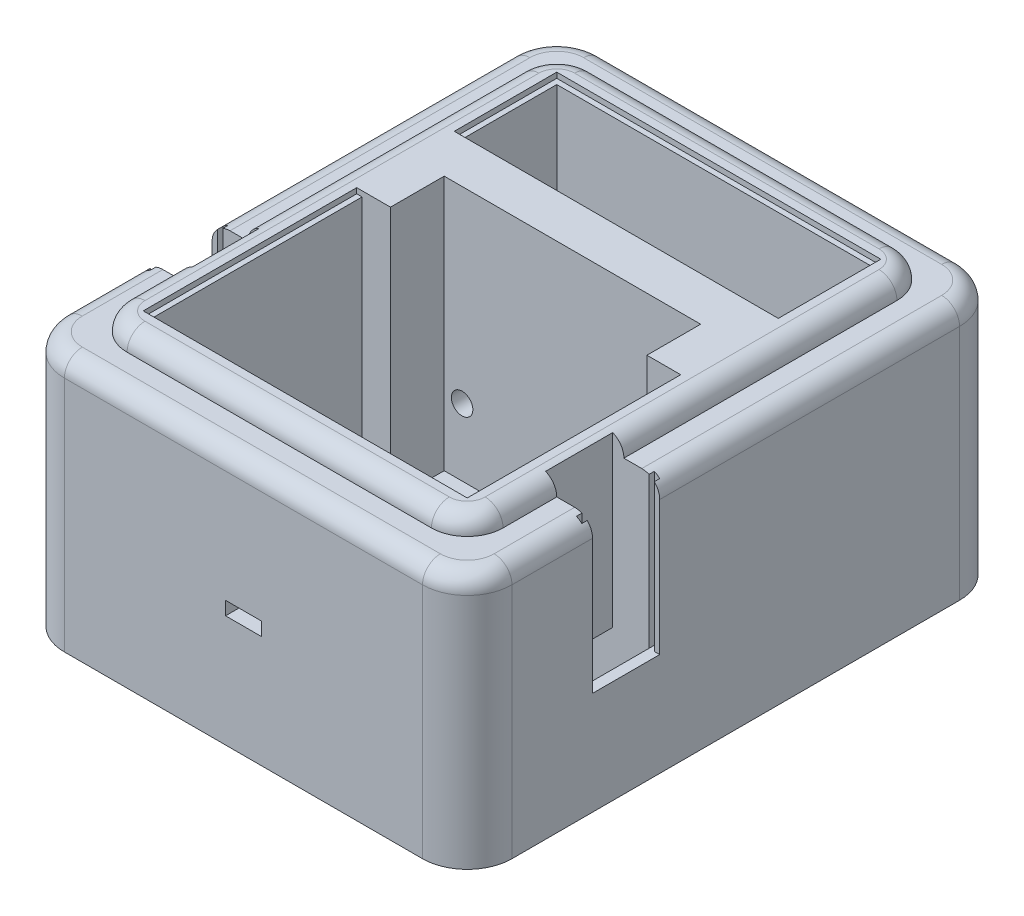
SolidWorks part; units mm, degrees
ref_plane "Přední rovina" through (0, 0, 0) normal (0, 0, 1) x (1, 0, 0)
ref_plane "Horní rovina" through (0, 0, 0) normal (0, 1, 0) x (1, 0, 0)
ref_plane "Pravá rovina" through (0, 0, 0) normal (1, 0, 0) x (0, 0, -1)
sketch "Skica2" plane through (0, 0, 0) normal (0, 1, 0) x (1, 0, 0)
  line L1 (0, 0) -> (100, 0)
  line L2 (0, 0) -> (0, 120)
  line L3 (0, 120) -> (100, 120)
  line L4 (100, 0) -> (100, 120)
  dimension "D1" = 120
  dimension "D2" = 100
extrude "Přidat vysunutím1" add sketch "Skica2" along normal blind 4
sketch "Skica3" plane through (0, 4, 0) normal (0, 1, 0) x (1, 0, 0)
  line L0 (0, 0) -> (100, 0) construction
  line L1 (0, 120) -> (15, 120)
  line L2 (0, 120) -> (0, 0)
  line L3 (0, 0) -> (15, 0)
  line L4 (15, 120) -> (15, 0)
  line L5 (100, 0) -> (100, 120) construction
  line L6 (0, 120) -> (100, 120)
  line L7 (0, 120) -> (0, 105)
  line L8 (0, 105) -> (100, 105)
  line L9 (100, 120) -> (100, 105)
  line L11 (100, 120) -> (85, 120)
  line L12 (100, 120) -> (100, 0)
  line L13 (100, 0) -> (85, 0)
  line L14 (85, 120) -> (85, 0)
  line L15 (100, 0) -> (0, 0)
  line L16 (100, 0) -> (100, 15)
  line L17 (100, 15) -> (0, 15)
  line L18 (0, 0) -> (0, 15)
  line L19 (15, 76.5) -> (85, 76.5)
  line L20 (15, 76.5) -> (15, 61.5)
  line L21 (15, 61.5) -> (85, 61.5)
  line L22 (85, 76.5) -> (85, 61.5)
  line L23 (21.35, 61.5) -> (78.65, 61.5)
  line L24 (21.35, 61.5) -> (21.35, 73.5)
  line L25 (21.35, 73.5) -> (78.65, 73.5)
  line L26 (78.65, 61.5) -> (78.65, 73.5)
  line L27 (15, 76.5) -> (85, 76.5)
  line L28 (15, 76.5) -> (15, 84.5)
  line L29 (15, 84.5) -> (85, 84.5)
  line L30 (85, 76.5) -> (85, 84.5)
  line L31 (21.35, 61.5) -> (15, 61.5)
  line L32 (21.35, 61.5) -> (21.35, 76.5)
  line L33 (21.35, 76.5) -> (15, 76.5)
  line L34 (15, 61.5) -> (15, 76.5)
  line L35 (78.65, 61.5) -> (85, 61.5)
  line L36 (78.65, 61.5) -> (78.65, 76.5)
  line L37 (78.65, 76.5) -> (85, 76.5)
  line L38 (85, 61.5) -> (85, 76.5)
  line L39 (78.65, 73.5) -> (21.35, 73.5)
  line L40 (78.65, 73.5) -> (78.65, 76.5)
  line L41 (78.65, 76.5) -> (21.35, 76.5)
  line L42 (21.35, 73.5) -> (21.35, 76.5)
  line M25 (0, 120) -> (0, 0)
  line M26 (0, 0) -> (100, 0)
  line M27 (100, 0) -> (100, 120)
  line M28 (100, 120) -> (0, 120)
  dimension "D1" = 15
  dimension "D2" = 15
  dimension "D3" = 15
  dimension "D4" = 15
  dimension "D5" = 15
  dimension "D6" = 70
  dimension "D7" = 12
  dimension "D8" = 57.3
  dimension "D9" = 6.35
  dimension "D10" = 28.5
  dimension "D11" = 8
  dimension "D12" = 70
extrude "Přidat vysunutím2" add sketch "Skica3" along normal blind 50 contours L8 L4 M25 M28 | L14 L6 L4 L8 | L17 L4 L8 L2 | L14 L8 M28 M27 | L17 L12 L8 L14 | L29 L4 L19 L27 L14 | L4 L17 M25 M26 | L14 L17 L4 M26 | L17 L14 M27 M26 | L24 L32 L19 L4 L21 | L25 L36 L27 L32 | L36 L26 L21 L14 L19
sketch "Skica4" plane through (0, 4, 0) normal (0, 1, 0) x (1, 0, 0)
  line L1 (15, 105) -> (85, 105)
  line L2 (15, 105) -> (15, 84.5)
  line L3 (15, 84.5) -> (85, 84.5)
  line L4 (85, 105) -> (85, 84.5)
extrude "Přidat vysunutím3" add sketch "Skica4" along normal blind 23
sketch "Skica8" plane through (0, 0, -61.5) normal (0, 0, 1) x (1, 0, 0)
  line L0 (78.65, 54) -> (78.65, 4) construction
  line L1 (78.65, 33) -> (85, 33)
  line L2 (78.65, 33) -> (78.65, 27)
  line L3 (78.65, 27) -> (85, 27)
  line L4 (85, 33) -> (85, 27)
  line L5 (85, 54) -> (85, 4) construction
  line L6 (78.65, 54) -> (85, 54) construction
  dimension "D1" = 6
  dimension "D2" = 21
extrude "Odebrat vysunutím1" cut sketch "Skica8" against normal blind 23
sketch "Skica9" plane through (0, 27, 0) normal (0, 1, 0) x (1, 0, 0)
  line L1 (78.65, 61.5) -> (85, 61.5)
  line L2 (78.65, 61.5) -> (78.65, 63.5)
  line L3 (78.65, 63.5) -> (85, 63.5)
  line L4 (85, 61.5) -> (85, 63.5)
  line L5 (85, 61.5) -> (85, 105) construction
  dimension "D1" = 2
  dimension "D2" = 6.35
extrude "Přidat vysunutím5" add sketch "Skica9" along normal blind 6
sketch "Skica10" plane through (0, 0, -73.5) normal (0, 0, 1) x (1, 0, 0)
  line L0 (21.35, 54) -> (78.65, 54) construction
  line L1 (78.65, 27) -> (78.65, 4) construction
  line L2 (21.35, 54) -> (21.35, 4) construction
  circle A0 centre (25.35, 19) radius 2.4
  circle A1 centre (74.65, 19) radius 2.4
  dimension "D1" = 4.8
  dimension "D2" = 4.8
  dimension "D5" = 4
  dimension "D6" = 4
  dimension "D3" = 35
  dimension "D4" = 35
extrude "Odebrat vysunutím2" cut sketch "Skica10" against normal blind 8
sketch "Skica11" plane through (0, 0, -15) normal (0, 0, -1) x (-1, 0, 0)
  line L0 (-85, 4) -> (-15, 4) construction
  line L1 (-58.3, 30.8) -> (-41.7, 30.8)
  line L2 (-58.3, 30.8) -> (-58.3, 19)
  line L3 (-58.3, 19) -> (-41.7, 19)
  line L4 (-41.7, 30.8) -> (-41.7, 19)
  line L5 (-15, 54) -> (-15, 4) construction
  dimension "D1" = 11.8
  dimension "D2" = 16.6
  dimension "D3" = 15
  dimension "26.7" = 26.7
extrude "Odebrat vysunutím5" cut sketch "Skica11" against normal blind 10
sketch "Skica14" plane through (0, 0, 0) normal (0, 0, 1) x (1, 0, 0)
  line L0 (0, 0) -> (100, 0) construction
  line L1 (46, 28) -> (54, 28)
  line L2 (46, 28) -> (46, 25)
  line L3 (46, 25) -> (54, 25)
  line L4 (54, 28) -> (54, 25)
  line L5 (0, 54) -> (0, 0) construction
  dimension "D1" = 3
  dimension "D2" = 8
  dimension "D3" = 25
  dimension "D4" = 46
extrude "Odebrat vysunutím6" cut sketch "Skica14" against normal blind 5
sketch "Skica15" plane through (0, 54, 0) normal (0, 1, 0) x (1, 0, 0)
  line L0 (0, 0) -> (100, 0) construction
  line L1 (0, 120) -> (8, 120)
  line L2 (0, 120) -> (0, 0)
  line L3 (0, 0) -> (8, 0)
  line L4 (8, 120) -> (8, 0)
  line L5 (100, 120) -> (0, 120) construction
  line L6 (100, 0) -> (0, 0)
  line L7 (100, 0) -> (100, 8)
  line L8 (100, 8) -> (0, 8)
  line L9 (0, 0) -> (0, 8)
  line L10 (100, 0) -> (92, 0)
  line L11 (100, 0) -> (100, 120)
  line L12 (100, 120) -> (92, 120)
  line L13 (92, 0) -> (92, 120)
  line L15 (0, 120) -> (100, 120)
  line L16 (0, 120) -> (0, 112)
  line L17 (0, 112) -> (100, 112)
  line L18 (100, 120) -> (100, 112)
  dimension "D1" = 8
  dimension "D2" = 8
  dimension "D3" = 8
  dimension "D4" = 8
extrude "Odebrat vysunutím7" cut sketch "Skica15" against normal blind 4
sketch "Skica20" plane through (0, 0, 0) normal (-1, 0, 0) x (0, 0, 1)
  line L0 (-112, 54) -> (-8, 54) construction
  line L1 (-43, 54) -> (-28, 54)
  line L2 (-43, 54) -> (-43, 23)
  line L3 (-43, 23) -> (-28, 23)
  line L4 (-28, 54) -> (-28, 23)
  line L6 (-8, 50) -> (-8, 54) construction
  dimension "D1" = 31
  dimension "D2" = 15
  dimension "D3" = 20
extrude "Odebrat vysunutím8" cut sketch "Skica20" against normal blind 10
sketch "Skica21" plane through (100, 0, 0) normal (1, 0, 0) x (0, 0, -1)
  line L0 (8, 54) -> (112, 54) construction
  line L1 (28, 54) -> (43, 54)
  line L2 (28, 54) -> (28, 23)
  line L3 (28, 23) -> (43, 23)
  line L4 (43, 54) -> (43, 23)
  line L5 (8, 50) -> (8, 54) construction
  dimension "D1" = 31
  dimension "D2" = 15
  dimension "D3" = 20
extrude "Odebrat vysunutím10" cut sketch "Skica21" against normal blind 10
sketch "Skica22" plane through (10, 0, 0) normal (-1, 0, 0) x (0, 0, 1)
  line L0 (-43, 54) -> (-43, 23) construction
  line L1 (-43, 23) -> (-28, 23) construction
  circle A0 centre (-35.5, 31.3) radius 2.2
  dimension "D1" = 4.4
  dimension "D2" = 7.5
  dimension "D3" = 8.3
extrude "Odebrat vysunutím11" cut sketch "Skica22" against normal blind 3
sketch "Skica23" plane through (90, 0, 0) normal (1, 0, 0) x (0, 0, -1)
  line L0 (28, 50) -> (28, 23) construction
  line L1 (28, 23) -> (43, 23) construction
  circle A0 centre (35.5, 31.3) radius 2.2
  dimension "D1" = 4.4
  dimension "D2" = 7.5
  dimension "D3" = 8.3
extrude "Odebrat vysunutím12" cut sketch "Skica23" against normal blind 3
sketch "Skica24" plane through (0, 50, 0) normal (0, 1, 0) x (1, 0, 0)
  line L0 (10, 28) -> (0, 28) construction
  line L1 (1.2, 28) -> (2.4, 28)
  line L2 (1.2, 28) -> (1.2, 26.8)
  line L3 (1.2, 26.8) -> (2.4, 26.8)
  line L4 (2.4, 28) -> (2.4, 26.8)
  line L5 (0, 28) -> (0, 0) construction
  line L6 (10, 43) -> (0, 43) construction
  line L7 (1.2, 43) -> (2.4, 43)
  line L8 (1.2, 43) -> (1.2, 44.2)
  line L9 (1.2, 44.2) -> (2.4, 44.2)
  line L10 (2.4, 43) -> (2.4, 44.2)
  line L11 (0, 120) -> (0, 43) construction
  line L12 (92, 28) -> (100, 28) construction
  line L13 (97.6, 28) -> (98.8, 28)
  line L14 (97.6, 28) -> (97.6, 26.8)
  line L15 (97.6, 26.8) -> (98.8, 26.8)
  line L16 (98.8, 28) -> (98.8, 26.8)
  line L17 (100, 43) -> (92, 43) construction
  line L18 (97.6, 43) -> (98.8, 43)
  line L19 (97.6, 43) -> (97.6, 44.2)
  line L20 (97.6, 44.2) -> (98.8, 44.2)
  line L21 (98.8, 43) -> (98.8, 44.2)
  line L22 (100, 0) -> (100, 28) construction
  line L23 (100, 43) -> (100, 120) construction
  dimension "D1" = 1.2
  dimension "D2" = 1.2
  dimension "D3" = 1.2
  dimension "D4" = 1.2
  dimension "D5" = 1.2
  dimension "D6" = 1.2
  dimension "D7" = 1.2
  dimension "D8" = 1.2
  dimension "D9" = 1.2
extrude "Odebrat vysunutím14" cut sketch "Skica24" against normal blind 27
sketch "Skica26" plane through (0, 23, 0) normal (0, 1, 0) x (1, 0, 0)
  line L0 (15, 61.5) -> (15, 15) construction
  line L1 (2.4, 43) -> (15, 43)
  line L2 (2.4, 43) -> (2.4, 28)
  line L3 (2.4, 28) -> (15, 28)
  line L4 (15, 43) -> (15, 28)
  line L5 (85, 61.5) -> (85, 15) construction
  line L6 (97.6, 43) -> (85, 43)
  line L7 (97.6, 43) -> (97.6, 28)
  line L8 (97.6, 28) -> (85, 28)
  line L9 (85, 43) -> (85, 28)
  line L10 (85, 15) -> (15, 15) construction
  line L12 (85, 15) -> (15, 15) construction
  dimension "D1" = 13
  dimension "D2" = 13
extrude "Odebrat vysunutím16" cut sketch "Skica26" against normal blind 19
sketch "Skica32" plane through (13, 0, 0) normal (-1, 0, 0) x (0, 0, 1)
  circle A0 centre (-35.5, 31.3) radius 2.2
extrude "Odebrat vysunutím19" cut sketch "Skica32" against normal through all
sketch "Skica33" plane through (78.65, 0, 0) normal (-1, 0, 0) x (0, 0, 1)
  line L0 (-61.5, 54) -> (-61.5, 4) construction
  line L1 (-63.5, 33) -> (-61.5, 33)
  line L2 (-63.5, 33) -> (-63.5, 27)
  line L3 (-63.5, 27) -> (-61.5, 27)
  line L4 (-61.5, 33) -> (-61.5, 27)
extrude "Odebrat vysunutím20" cut sketch "Skica33" against normal up to surface (6.35 mm away) up to face at (85, 31.3, -37.7)
sketch "Skica35" plane through (0, 19, 0) normal (0, 1, 0) x (1, 0, 0)
  line L1 (41.7, 15) -> (58.3, 15)
  line L2 (41.7, 15) -> (41.7, 5)
  line L3 (41.7, 5) -> (58.3, 5)
  line L4 (58.3, 15) -> (58.3, 5)
extrude "Odebrat vysunutím21" cut sketch "Skica35" against normal blind 1.5
sketch "Skica38" plane through (0, 27, 0) normal (0, 1, 0) x (1, 0, 0)
  line L1 (78.65, 61.5) -> (79.65, 61.5)
  line L2 (78.65, 61.5) -> (78.65, 84.5)
  line L3 (78.65, 84.5) -> (79.65, 84.5)
  line L4 (79.65, 61.5) -> (79.65, 84.5)
  dimension "D1" = 1
extrude "Přidat vysunutím9" add sketch "Skica38" along normal blind 15
sketch "Skica39" plane through (0, 0, -61.5) normal (0, 0, 1) x (1, 0, 0)
  line L1 (79.65, 33) -> (85, 33)
  line L2 (79.65, 33) -> (79.65, 38)
  line L3 (79.65, 38) -> (85, 38)
  line L4 (85, 33) -> (85, 38)
  line L5 (85, 54) -> (85, 33) construction
  dimension "D1" = 5
  dimension "D2" = 5.35
extrude "Odebrat vysunutím23" cut sketch "Skica39" against normal up to surface (23 mm away) up to face at (59.8833, 38, -84.5)
sketch "Skica40" plane through (10, 0, 0) normal (-1, 0, 0) x (0, 0, 1)
  line L1 (-43, 54) -> (-28, 54)
  line L2 (-43, 54) -> (-43, 23)
  line L3 (-43, 23) -> (-28, 23)
  line L4 (-28, 54) -> (-28, 23)
extrude "Odebrat vysunutím24" cut sketch "Skica40" against normal blind 0.5
sketch "Skica41" plane through (90, 0, 0) normal (1, 0, 0) x (0, 0, -1)
  line L1 (28, 23) -> (43, 23)
  line L2 (28, 23) -> (28, 54)
  line L3 (28, 54) -> (43, 54)
  line L4 (43, 23) -> (43, 54)
extrude "Odebrat vysunutím25" cut sketch "Skica41" against normal blind 0.5
sketch "Skica43" plane through (0, 54, 0) normal (0, 1, 0) x (1, 0, 0)
  line L0 (92, 8) -> (8, 8) construction
  line L1 (8, 112) -> (85, 112)
  line L2 (8, 112) -> (8, 105)
  line L3 (8, 105) -> (85, 105)
  line L4 (85, 112) -> (85, 105)
  line L5 (85, 8) -> (92, 8)
  line L6 (85, 8) -> (85, 112)
  line L7 (85, 112) -> (92, 112)
  line L8 (92, 8) -> (92, 112)
  line L9 (15, 84.5) -> (85, 84.5) construction
  line L10 (8, 105) -> (15, 105)
  line L11 (8, 105) -> (8, 15)
  line L12 (8, 15) -> (15, 15)
  line L13 (15, 105) -> (15, 15)
  line L14 (8, 15) -> (85, 15)
  line L15 (8, 15) -> (8, 8)
  line L16 (8, 8) -> (85, 8)
  line L17 (85, 15) -> (85, 8)
  line L18 (78.65, 61.5) -> (85, 61.5)
  line L19 (78.65, 61.5) -> (78.65, 84.5)
  line L20 (78.65, 84.5) -> (85, 84.5)
  line L21 (85, 61.5) -> (85, 84.5)
  line L23 (15, 61.5) -> (21.35, 61.5)
  line L24 (15, 61.5) -> (15, 73.5)
  line L25 (15, 73.5) -> (21.35, 73.5)
  line L26 (21.35, 61.5) -> (21.35, 73.5)
  line L27 (78.65, 84.5) -> (15, 84.5)
  line L28 (78.65, 84.5) -> (78.65, 73.5)
  line L29 (78.65, 73.5) -> (15, 73.5)
  line L30 (15, 84.5) -> (15, 73.5)
extrude "Přidat vysunutím10" add sketch "Skica43" along normal blind 7 contours L4 L5 L3 L24 | L13 L23 L3 L5 L6 L7 L8 L9 L12 L15 | L19 L12 L6 L21 | L6 L10 L11 L0 L1 L2 L3 L4 L20 L13 | L13 L25 L18 L19 L21 | L25 L13 L16 L17 | L12 L9 L10 L6 L14
sketch "Skica44" plane through (0, 50, 0) normal (0, 1, 0) x (1, 0, 0)
  line L0 (8, 28) -> (8, 8) construction
  line L1 (0, 120) -> (2.4, 120)
  line L2 (0, 120) -> (0, 44.2)
  line L3 (0, 44.2) -> (2.4, 44.2)
  line L4 (2.4, 120) -> (2.4, 44.2)
  line L5 (0, 43) -> (1.2, 43)
  line L6 (0, 43) -> (0, 44.2)
  line L7 (0, 44.2) -> (1.2, 44.2)
  line L8 (1.2, 43) -> (1.2, 44.2)
  line L9 (0, 28) -> (1.2, 28)
  line L10 (0, 28) -> (0, 26.8)
  line L11 (0, 26.8) -> (1.2, 26.8)
  line L12 (1.2, 28) -> (1.2, 26.8)
  line L13 (2.4, 28) -> (8, 28)
  line L14 (2.4, 28) -> (2.4, 26.8)
  line L15 (2.4, 26.8) -> (8, 26.8)
  line L16 (8, 28) -> (8, 26.8)
  line L17 (92, 43) -> (92, 112) construction
  line L18 (8, 8) -> (0, 8)
  line L19 (8, 8) -> (8, 26.8)
  line L20 (8, 26.8) -> (0, 26.8)
  line L21 (0, 8) -> (0, 26.8)
  line L22 (0, 8) -> (100, 8)
  line L23 (0, 8) -> (0, 0)
  line L24 (0, 0) -> (100, 0)
  line L25 (100, 8) -> (100, 0)
  line L26 (92, 28) -> (97.6, 28)
  line L27 (92, 28) -> (92, 26.8)
  line L28 (92, 26.8) -> (97.6, 26.8)
  line L29 (97.6, 28) -> (97.6, 26.8)
  line L30 (100, 28) -> (98.8, 28)
  line L31 (100, 28) -> (100, 26.8)
  line L32 (100, 26.8) -> (98.8, 26.8)
  line L33 (98.8, 28) -> (98.8, 26.8)
  line L34 (92, 26.8) -> (100, 26.8)
  line L35 (92, 26.8) -> (92, 8)
  line L36 (92, 8) -> (100, 8)
  line L37 (100, 26.8) -> (100, 8)
  line L38 (100, 43) -> (98.8, 43)
  line L39 (100, 43) -> (100, 44.2)
  line L40 (100, 44.2) -> (98.8, 44.2)
  line L41 (98.8, 43) -> (98.8, 44.2)
  line L42 (97.6, 43) -> (92, 43)
  line L43 (97.6, 43) -> (97.6, 44.2)
  line L44 (97.6, 44.2) -> (92, 44.2)
  line L45 (92, 43) -> (92, 44.2)
  line L47 (92, 44.2) -> (100, 44.2)
  line L48 (92, 44.2) -> (92, 120)
  line L49 (92, 120) -> (100, 120)
  line L50 (100, 44.2) -> (100, 120)
  line L51 (2.4, 120) -> (92, 120)
  line L52 (2.4, 120) -> (2.4, 112)
  line L53 (2.4, 112) -> (92, 112)
  line L54 (92, 120) -> (92, 112)
  line L55 (8, 43) -> (2.4, 43)
  line L56 (8, 43) -> (8, 112)
  line L57 (8, 112) -> (2.4, 112)
  line L58 (2.4, 43) -> (2.4, 112)
  line M1 (1.2, 43) -> (1.2, 44.2)
  line M3 (2.4, 44.2) -> (2.4, 43)
  line M4 (2.4, 43) -> (8, 43)
  line M5 (8, 43) -> (8, 112)
  line M6 (8, 112) -> (92, 112)
  line M7 (92, 112) -> (92, 43)
  line M8 (92, 43) -> (97.6, 43)
  line M9 (97.6, 43) -> (97.6, 44.2)
  line M10 (97.6, 44.2) -> (98.8, 44.2)
  line M11 (98.8, 44.2) -> (98.8, 43)
  line M12 (98.8, 43) -> (100, 43)
  line M13 (100, 43) -> (100, 120)
  line M14 (100, 120) -> (0, 120)
  line M15 (0, 120) -> (0, 43)
  line M16 (0, 43) -> (1.2, 43)
extrude "Přidat vysunutím11" add sketch "Skica44" along normal blind 7 contours L25 L22 L18 L23 L24 | L48 L44 L40 M7 M10 M13 M14 | L53 L4 M3 M4 M5 | L4 L53 L48 M6 M14 | L29 L26 L27 L28 | L30 L33 L32 L31 | L37 L32 L34 L28 L35 L22 | L40 M13 M11 M12 | L44 M9 M7 M8 | L21 L18 L19 L15 L20 L11 | L12 L9 L10 L11 | L16 L13 L14 L15 | L3 M15 M16 M1
sketch "Skica45" plane through (0, 61, 0) normal (0, 1, 0) x (1, 0, 0)
  line L0 (85, 61.5) -> (85, 105) construction
  line L1 (15, 105) -> (85, 105)
  line L2 (15, 105) -> (15, 106.2)
  line L3 (15, 106.2) -> (85, 106.2)
  line L4 (85, 105) -> (85, 106.2)
  line L6 (15, 84.5) -> (13.8, 84.5)
  line L7 (15, 84.5) -> (15, 106.2)
  line L8 (15, 106.2) -> (13.8, 106.2)
  line L9 (13.8, 84.5) -> (13.8, 106.2)
  line L10 (13.8, 84.5) -> (85, 84.5)
  line L11 (13.8, 84.5) -> (13.8, 83.3)
  line L12 (13.8, 83.3) -> (85, 83.3)
  line L13 (85, 84.5) -> (85, 83.3)
  line L14 (85, 106.2) -> (86.2, 106.2)
  line L15 (85, 106.2) -> (85, 83.3)
  line L16 (85, 83.3) -> (86.2, 83.3)
  line L17 (86.2, 106.2) -> (86.2, 83.3)
  line L18 (15, 15) -> (13.8, 15)
  line L19 (15, 15) -> (15, 61.5)
  line L20 (15, 61.5) -> (13.8, 61.5)
  line L21 (13.8, 15) -> (13.8, 61.5)
  line L22 (85, 15) -> (13.8, 15)
  line L23 (85, 15) -> (85, 13.8)
  line L24 (85, 13.8) -> (13.8, 13.8)
  line L25 (13.8, 15) -> (13.8, 13.8)
  line L26 (85, 61.5) -> (86.2, 61.5)
  line L27 (85, 61.5) -> (85, 13.8)
  line L28 (85, 13.8) -> (86.2, 13.8)
  line L29 (86.2, 61.5) -> (86.2, 13.8)
  dimension "D1" = 1.2
  dimension "D2" = 1.2
  dimension "D3" = 1.2
  dimension "D4" = 71.2
  dimension "D5" = 1.2
  dimension "D6" = 1.2
  dimension "D7" = 71.2
  dimension "D8" = 1.2
  dimension "D9" = 1.2
  dimension "D10" = 0
  dimension "D11" = 46.5
  dimension "D12" = 21.7
extrude "Odebrat vysunutím26" cut sketch "Skica45" against normal blind 1.2 contours L21 L20 L19 L18 | L24 L25 L22 L23 | L27 L28 L29 L26 | L9 L8 L7 L6 | L3 L2 L1 L4 | L10 L13 L12 L11 | L15 L16 L17 L14
fillet "Zaoblit1" radius 10 4 edges at (100, 28.5, 0) (100, 28.5, -120) (0, 28.5, -120) (0, 28.5, 0)
fillet "Zaoblit2" radius 8 4 edges at (8, 59, -8) (8, 59, -112) (92, 59, -112) (92, 59, -8)
fillet "Zaoblit3" radius 4 50 edges at (8, 59, -43) (92, 59, -28) (8, 61, -22) (90.75, 61, -28) (89.5, 61, -35.5) (90.75, 61, -43) (92, 61, -73.5) (9.25, 61, -43) (10.5, 61, -35.5) (9.25, 61, -28) (8, 59, -28) (100, 57, -19) (97.6, 57, -27.4) (1.8, 57, -26.8) (1.2, 57, -27.4) (98.8, 57, -27.4) (98.2, 57, -26.8) (2.4, 57, -27.4) (0, 57, -19) (92, 59, -43) (98.2, 57, -44.2) (97.6, 57, -43.6) (98.8, 57, -43.6) (100, 57, -76.5) (1.2, 57, -43.6) (1.8, 57, -44.2) (2.4, 57, -43.6) (50, 57, 0) (2.9289, 57, -2.9289) (97.0711, 57, -2.9289) (50, 57, -120) (0, 57, -76.5) (2.9289, 57, -117.0711) (97.0711, 57, -117.0711) (8, 59, -16) (50, 61, -8) (92, 61, -22) (50, 61, -112) (8, 61, -73.5) (89.6569, 61, -10.3431) (89.6569, 61, -109.6569) (10.3431, 61, -109.6569) (10.3431, 61, -10.3431) (84, 59, -8) (16, 59, -8) (84, 59, -112) (16, 59, -112) (8, 59, -104) (92, 59, -104) (92, 59, -16)
